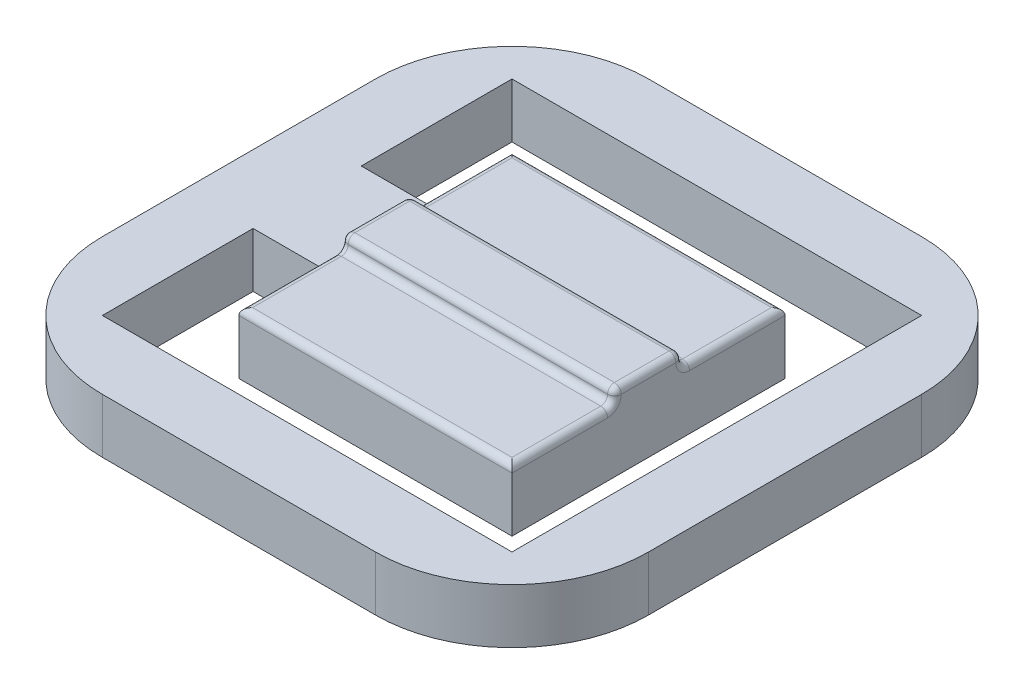
SolidWorks part; units mm, degrees
ref_plane "前视基准面" through (0, 0, 0) normal (0, 0, 1) x (1, 0, 0)
ref_plane "上视基准面" through (0, 0, 0) normal (0, 1, 0) x (1, 0, 0)
ref_plane "右视基准面" through (0, 0, 0) normal (1, 0, 0) x (0, 0, -1)
other "Configuration Table"
sketch "草图1" plane through (0, 0, 0) normal (0, 1, 0) x (1, 0, 0)
  line L0 (-10, 3.9606) -> (-15, 3.9606)
  line L1 (-10, -20) -> (10, -20)
  line L2 (-20, -10) -> (-20, 10)
  line L3 (-10, 20) -> (10, 20)
  line L4 (20, -10) -> (20, 10)
  line L5 (-20, -20) -> (20, 20) construction
  line L6 (-20, 20) -> (20, -20) construction
  line L7 (-15, 3.9606) -> (-15, 15)
  line L8 (-15, 15) -> (15, 15)
  line L9 (15, 15) -> (15, -15)
  line L10 (0, 0) -> (15, 0) construction
  line L11 (-10, 3.9606) -> (-10, 10)
  line L12 (-10, 10) -> (10, 10)
  line L13 (10, 10) -> (10, -10)
  line L14 (-10, -10) -> (10, -10)
  line L15 (-15, -15) -> (15, -15)
  line L16 (-10, -3.9606) -> (-10, -10)
  line L17 (-10, -3.9606) -> (-15, -3.9606)
  line L18 (-15, -3.9606) -> (-15, -15)
  arc A0 (10, -20) -> (20, -10) centre (10, -10) ccw
  arc A1 (-10, -20) -> (-20, -10) centre (-10, -10) cw
  arc A2 (-20, 10) -> (-10, 20) centre (-10, 10) cw
  arc A3 (10, 20) -> (20, 10) centre (10, 10) cw
  point P0 (0, 0)
  point P26 (10, 0)
  dimension "D3" = 10
  dimension "D1" = 40
  dimension "D2" = 40
  dimension "D4" = 30
extrude "凸台-拉伸1" add sketch "草图1" along normal blind 4
sketch "草图2" plane through (-10, 0, 0) normal (-1, 0, 0) x (0, 0, 1)
  line L0 (-10, 4) -> (10, 4)
  line L1 (10, 4) -> (10, 4.5)
  line L2 (10, 4.5) -> (2.5, 4.5)
  line L3 (2.5, 4.5) -> (2.5, 5.5)
  line L4 (2.5, 5.5) -> (-2.5, 5.5)
  line L5 (0, 5.5) -> (0, 0) construction
  line L6 (-10, 4) -> (-10, 4.5)
  line L7 (-10, 4.5) -> (-2.5, 4.5)
  line L8 (-2.5, 4.5) -> (-2.5, 5.5)
  dimension "D1" = 5
  dimension "D2" = 7.5
  dimension "D3" = 0.5
  dimension "D4" = 1
extrude "凸台-拉伸2" add sketch "草图2" against normal blind 20
fillet "圆角1" radius 0.5 12 edges at (10, 5, -2.5) (-10, 5, -2.5) (10, 5, 2.5) (-10, 5, 2.5) (0, 4.5, -10) (10, 4.5, -6.25) (0, 4.5, -2.5) (-10, 4.5, -6.25) (0, 4.5, 2.5) (10, 4.5, 6.25) (0, 4.5, 10) (-10, 4.5, 6.25)
fillet "圆角2" radius 0.5 8 edges at (9.8536, 5.5, 2.3536) (0, 5.5, 2.5) (-9.8536, 5.5, 2.3536) (-10, 5.5, 0) (-9.8536, 5.5, -2.3536) (0, 5.5, -2.5) (9.8536, 5.5, -2.3536) (10, 5.5, 0)
